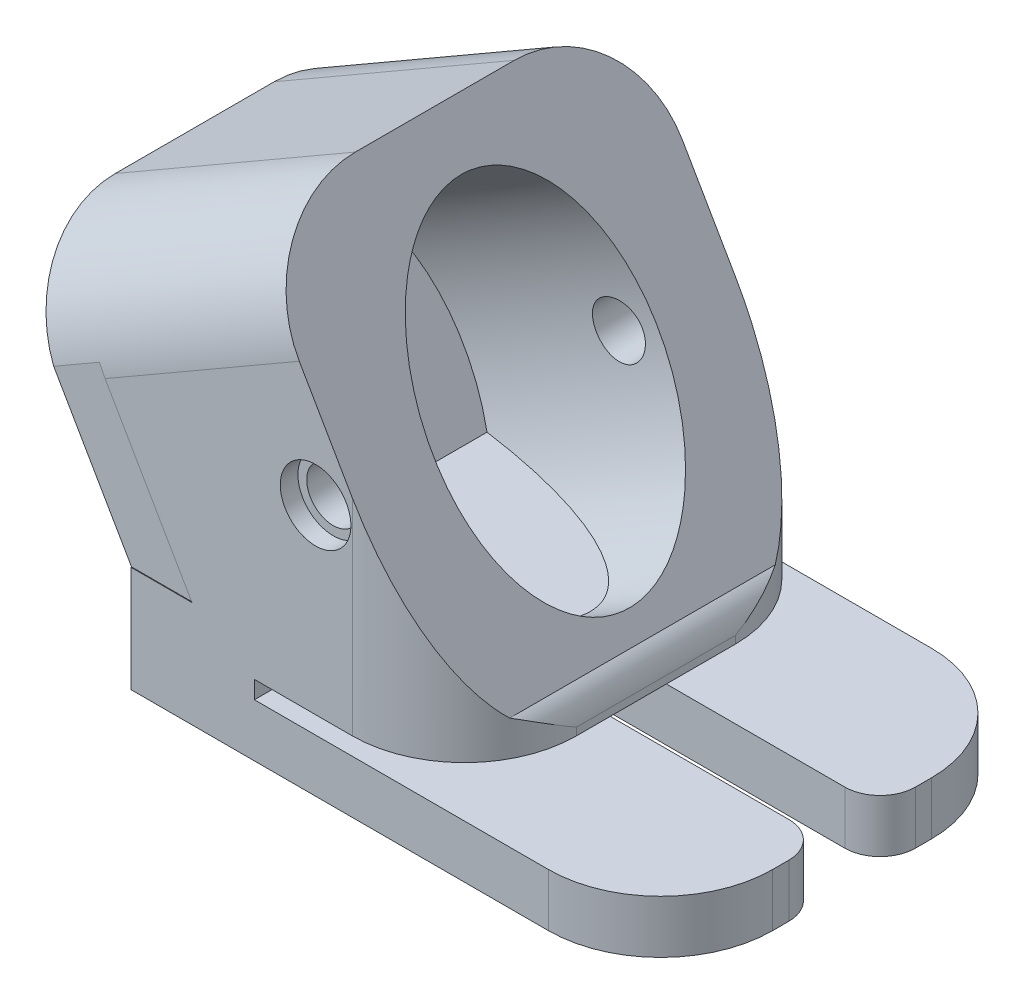
SolidWorks part; units mm, degrees
note: The reader was unsure of these and kept them because the rebuilt part matched: shared geometry of "Sketch7<3>".
ref_plane "Front Plane" through (0, 0, 0) normal (0, 0, 1) x (1, 0, 0)
ref_plane "Top Plane" through (0, 0, 0) normal (0, 1, 0) x (1, 0, 0)
ref_plane "Right Plane" through (0, 0, 0) normal (1, 0, 0) x (0, 0, -1)
sketch "Sketch1" plane through (0, 0, 0) normal (0, 0, 1) x (1, 0, 0)
  line L0 (0, 0) -> (16.4978, 9.525)
  line L1 (0, 0) -> (20.7767, 0) construction
  line L2 (12.7, 0) -> (19.6728, 4.0257)
  line L3 (19.6928, 3.9911) -> (16.4978, 9.525) construction
  point P9 (14.1735, 0.8507)
  dimension "D1" = 19.05
  dimension "D2" = 30
  dimension "D3" = 6.35
  dimension "D4" = 8.0515
  dimension "D5" = 6.35
ref_plane "Plane1" through (16.4978, 9.525, 0) normal (0.866, 0.5, 0) x (0, 0, -1)
sketch "Sketch2" plane through (16.4978, 9.525, 0) normal (0.866, 0.5, 0) x (0, 0, -1)
  line L0 (0, 100000) -> (0, -100010.3884) construction
  line L1 (10.85, 12.525) -> (10.85, -12.525)
  line L2 (10.85, 12.525) -> (-10.85, 12.525)
  line L3 (10.85, -12.525) -> (-10.85, -12.525)
  line L4 (-10.85, 12.525) -> (-10.85, -12.525)
  line L5 (10.85, 12.525) -> (-10.85, -12.525) construction
  line L6 (10.85, -12.525) -> (-10.85, 12.525) construction
  ellipse E0 centre (0, 0) end of major axis (0, 9.525) minor radius 6.35
  point P1 (-10.85, 0)
  point P7 (0, -12.525)
  dimension "D1" = 19.05
  dimension "D2" = 12.7
  dimension "D3" = 4.5
  dimension "D4" = 3
extrude "Boss-Extrude1" add sketch "Sketch2" against normal blind 12.7
sketch "Sketch3" plane through (5.4993, 3.175, 0) normal (-0.866, -0.5, 0) x (0, 0, 1)
  line L0 (-10.85, 12.525) -> (-10.85, -12.525)
  line L1 (-10.85, 12.525) -> (10.8107, 12.525)
  line L2 (-10.85, -12.525) -> (10.8107, -12.525)
  line L3 (10.8107, 12.525) -> (10.8107, -12.525)
extrude "Boss-Extrude2" add sketch "Sketch3" along normal blind 3
sketch "Sketch5" plane through (0, 0, 0) normal (0, 1, 0) x (-1, 0, 0)
  line L0 (-22.7603, 10.85) -> (-22.7603, -10.85)
  line L1 (-22.7603, 10.85) -> (-3.8682, 10.85)
  line L2 (-22.7603, -10.85) -> (-3.8682, -10.85)
  line L3 (-3.8682, 10.85) -> (-3.8682, -10.85)
  line L8 (-22.7603, 10.85) -> (-22.7603, -10.85) construction
extrude "Boss-Extrude3" add sketch "Sketch5" against normal blind 2
sketch "Sketch6" plane through (0, -2, 0) normal (0, -1, 0) x (1, 0, 0)
  line L0 (3.8682, -10.85) -> (3.8682, 10.85)
  line L1 (3.8682, -10.85) -> (33.8682, -10.85)
  line L2 (3.8682, 10.85) -> (33.8682, 10.85)
  line L3 (33.8682, -10.85) -> (33.8682, 10.85)
  line L10 (3.8682, 10.85) -> (8.487, 10.85) construction
  line L11 (3.8682, -10.85) -> (3.8682, 10.85) construction
  dimension "D1" = 30
extrude "Boss-Extrude4" add sketch "Sketch6" along normal blind 4
sketch "Sketch7" plane through (33.8682, 0, 0) normal (1, 0, 0) x (0, 0, -1)
  line L0 (-10.85, -2) -> (10.85, -2)
  line L1 (-10.85, -2) -> (-10.85, -3)
  line L2 (10.85, -2) -> (10.85, -3)
  line L3 (-10.85, -3) -> (10.85, -3)
  line L4 (-1.5875, -3) -> (1.5875, -3)
  line L5 (-10.85, -6) -> (-10.85, -2) construction
  line L6 (-10.85, -6) -> (10.85, -6)
  line L7 (-10.85, -6) -> (-10.85, -13.2725)
  line L8 (10.85, -6) -> (10.85, -13.2725)
  line L9 (-10.85, -13.2725) -> (10.85, -13.2725)
  line L10 (-1.5875, -3) -> (-1.5875, -6)
  line L11 (1.5875, -3) -> (1.5875, -6)
  line L12 (-1.5875, -6) -> (1.5875, -6)
  point P0 (0, -3)
  point P11 (0, -3)
  line M4 (-10.85, -6) -> (10.85, -6)
  dimension "D1" = 1
  dimension "D2" = 3.175
extrude "Cut-Extrude2" cut sketch "Sketch7" against normal blind 23 contours L2 L3 L1 L0 | L10 L12 L11 L4
extrude "Cut-Extrude3" cut sketch "Sketch7<3>" against normal through all contours L7 L9 L8 M4
sketch "Sketch7<3>" plane through (33.8682, 0, 0) normal (1, 0, 0) x (0, 0, -1) same geometry as "Sketch7"
ref_plane "Plane2" through (3.175, -5.4993, 0) normal (0.5, -0.866, 0) x (0.866, 0.5, 0)
sketch "Sketch8" plane through (3.175, -5.4993, 6.35) normal (0.5, -0.866, 0) x (0.75, 0.433, -0.5)
  line L0 (13.7985, 1.5003) -> (14.5485, 0.2012)
  line L1 (13.7985, 1.5003) -> (-3.522, -8.4997)
  line L2 (14.5485, 0.2012) -> (-2.772, -9.7988)
  line L3 (-3.522, -8.4997) -> (-2.772, -9.7988)
  line L4 (12.7, 0) -> (19.6728, 4.0257) construction
  dimension "D1" = 1.5
  dimension "D2" = 20
ref_plane "Plane3" through (19.6728, 0, 0) normal (1, 0, 0) x (0, 0, -1)
sketch "Sketch11" plane through (19.6728, 0.1949, 0) normal (-1, 0, 0) x (0, 0, -1)
  circle A0 centre (0, -3.8309) radius 1
  dimension "D1" = 2
extrude "Cut-Extrude8" cut sketch "Sketch11" along normal through all
sketch "Sketch9" plane through (0, 0, -10.85) normal (0, 0, -1) x (-1, 0, 0)
  line L0 (0, 0) -> (-16.4978, 9.525) construction
  line L1 (-10.2353, 20.372) -> (-21.997, 0) construction
  circle A0 centre (-14.3327, 8.275) radius 1.5
  dimension "D1" = 3
  dimension "D2" = 2.5
extrude "Cut-Extrude4" cut sketch "Sketch9" against normal up to next contours A0
sketch "Sketch10" plane through (0, 0, -10.85) normal (0, 0, -1) x (-1, 0, 0)
  circle A0 centre (-14.3327, 8.275) radius 2
  dimension "D1" = 4
extrude "Cut-Extrude7" cut sketch "Sketch10" against normal blind 1
mirror "Mirror1" about plane through (0, 0, 0) normal (0, 0, 1) of "Cut-Extrude7", "Cut-Extrude4"
fillet "Fillet5" radius 6.35 6 edges at (33.8682, -4.5, 10.85) (33.8682, -4.5, -10.85) (22.7603, -1, -10.85) (22.7603, -1, 10.85) (4.736, 17.197, 10.85) (3.437, 16.447, -10.85)
fillet "Fillet6" radius 2 2 edges at (33.8682, -4.5, -1.5875) (33.8682, -4.5, 1.5875)
fillet "Fillet7" radius 2 1 edges at (22.7603, 0, 0)
